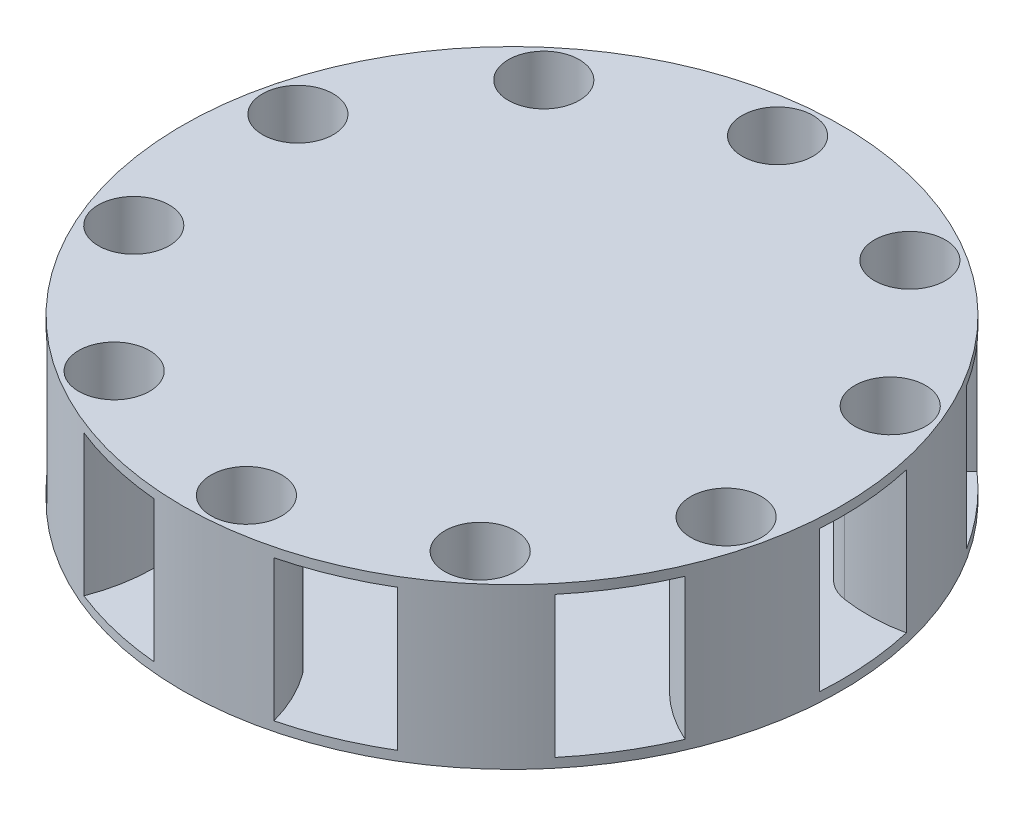
SolidWorks part; units mm, degrees
material "6061 Alloy"
ref_plane "Front Plane" through (0, 0, 0) normal (0, 0, 1) x (1, 0, 0)
ref_plane "Top Plane" through (0, 0, 0) normal (0, 1, 0) x (1, 0, 0)
ref_plane "Right Plane" through (0, 0, 0) normal (1, 0, 0) x (0, 0, -1)
sketch "Sketch1" plane through (0, 0, 0) normal (0, 1, 0) x (1, 0, 0)
  circle A0 centre (0, 0) radius 70
  dimension "D1" = 140
extrude "Boss-Extrude1" add sketch "Sketch1" against normal blind 2
sketch "Sketch2" plane through (0, 0, 0) normal (0, 1, 0) x (1, 0, 0)
  circle A0 centre (-56.7785, -23.5664) radius 8.525
  circle A1 centre (-56.7785, -23.5664) radius 7.525
  circle A2 centre (-59.7868, 14.308) radius 8.525
  circle A3 centre (-59.7868, 14.308) radius 7.525
  circle A4 centre (-39.9585, 46.7172) radius 8.525
  circle A5 centre (-39.9585, 46.7172) radius 7.525
  circle A6 centre (-4.8674, 61.282) radius 8.525
  circle A7 centre (-4.8674, 61.282) radius 7.525
  circle A8 centre (32.0828, 52.4392) radius 8.525
  circle A9 centre (32.0828, 52.4392) radius 7.525
  circle A10 centre (56.7785, 23.5664) radius 8.525
  circle A11 centre (56.7785, 23.5664) radius 7.525
  circle A12 centre (59.7868, -14.308) radius 8.525
  circle A13 centre (59.7868, -14.308) radius 7.525
  circle A14 centre (39.9585, -46.7172) radius 8.525
  circle A15 centre (39.9585, -46.7172) radius 7.525
  circle A16 centre (4.8674, -61.282) radius 8.525
  circle A17 centre (4.8674, -61.282) radius 7.525
  circle A18 centre (-32.0828, -52.4392) radius 8.525
  circle A19 centre (-32.0828, -52.4392) radius 7.525
  point P34 (0, 0)
  dimension "D1" = 17.05
  dimension "D2" = 61.475
  dimension "D3" = 15.05
  dimension "D4" = 10
extrude "Cut-Extrude1" cut sketch "Sketch2" against normal blind 2 contours A3 | A5 | A7 | A9 | A11 | A13 | A15 | A17 | A19 | A1
sketch "Sketch3" plane through (0, 0, 0) normal (0, 1, 0) x (1, 0, 0)
  arc A0 (-42.6484, 38.6277) -> (-31.5498, 48.1207) centre (-39.9585, 46.7172) ccw
  arc A1 (-11.7985, 56.3186) -> (2.7603, 57.4749) centre (-4.8674, 61.282) ccw
  arc A2 (23.558, 52.4977) -> (36.016, 44.8758) centre (32.0828, 52.4392) ccw
  arc A3 (49.9162, 28.6245) -> (55.5149, 15.1356) centre (56.7785, 23.5664) ccw
  arc A4 (57.2081, -6.1823) -> (53.8089, -20.3859) centre (59.7868, -14.308) ccw
  arc A5 (42.6484, -38.6277) -> (31.5498, -48.1207) centre (39.9585, -46.7172) ccw
  arc A6 (11.7985, -56.3186) -> (-2.7603, -57.4749) centre (4.8674, -61.282) ccw
  arc A7 (-23.558, -52.4977) -> (-36.016, -44.8758) centre (-32.0828, -52.4392) ccw
  arc A8 (-49.9162, -28.6245) -> (-55.5149, -15.1356) centre (-56.7785, -23.5664) ccw
  arc A9 (-57.2081, 6.1823) -> (-53.8089, 20.3859) centre (-59.7868, 14.308) ccw
  circle A10 centre (-59.7868, 14.308) radius 6.525
  circle A11 centre (-39.9585, 46.7172) radius 6.525
  circle A12 centre (-4.8674, 61.282) radius 6.525
  circle A13 centre (32.0828, 52.4392) radius 6.525
  circle A14 centre (56.7785, 23.5664) radius 6.525
  circle A15 centre (59.7868, -14.308) radius 6.525
  circle A16 centre (39.9585, -46.7172) radius 6.525
  circle A17 centre (4.8674, -61.282) radius 6.525
  circle A18 centre (-32.0828, -52.4392) radius 6.525
  circle A19 centre (-56.7785, -23.5664) radius 6.525
  arc A20 (23.5578, 52.4392) -> (25.9098, 65.0283) centre (58.9194, 52.3471) cw
  circle A21 centre (0, 0) radius 70 construction
  arc A22 (35.964, 44.8489) -> (46.102, 52.6745) centre (19.7828, 76.2913) ccw
  arc A23 (46.102, 52.6745) -> (25.9098, 65.0283) centre (0, 0) ccw
  arc A24 (49.8817, 28.5772) -> (59.1841, 37.3796) centre (78.4357, 7.7177) cw
  arc A25 (55.4571, 15.1444) -> (68.2586, 15.5165) centre (60.8475, 50.0929) ccw
  arc A26 (68.2586, 15.5165) -> (59.1841, 37.3796) centre (0, 0) ccw
  arc A27 (57.1524, -6.2002) -> (69.8522, -4.5468) centre (67.9922, -39.8596) cw
  arc A28 (53.7674, -20.3447) -> (64.3427, -27.5683) centre (78.6705, 4.7607) ccw
  arc A29 (64.3427, -27.5683) -> (69.8522, -4.5468) centre (0, 0) ccw
  arc A30 (42.5929, -38.6094) -> (53.8391, -44.7365) centre (31.5779, -72.2118) cw
  arc A31 (31.5404, -48.0629) -> (35.8501, -60.1229) centre (66.4441, -42.3899) ccw
  arc A32 (35.8501, -60.1229) -> (53.8391, -44.7365) centre (0, 0) ccw
  arc A33 (11.7643, -56.2711) -> (17.2613, -67.8384) centre (-16.898, -76.9817) cw
  arc A34 (-2.734, -57.4227) -> (-6.336, -69.7127) centre (28.8382, -73.349) ccw
  arc A35 (-6.336, -69.7127) -> (17.2613, -67.8384) centre (0, 0) ccw
  arc A36 (-23.5578, -52.4392) -> (-25.9098, -65.0283) centre (-58.9194, -52.3471) cw
  arc A37 (-35.964, -44.8489) -> (-46.102, -52.6745) centre (-19.7828, -76.2913) ccw
  arc A38 (-46.102, -52.6745) -> (-25.9098, -65.0283) centre (0, 0) ccw
  arc A39 (-49.8817, -28.5772) -> (-59.1841, -37.3796) centre (-78.4357, -7.7177) cw
  arc A40 (-55.4571, -15.1444) -> (-68.2586, -15.5165) centre (-60.8475, -50.0929) ccw
  arc A41 (-68.2586, -15.5165) -> (-59.1841, -37.3796) centre (0, 0) ccw
  arc A42 (-57.1524, 6.2002) -> (-69.8522, 4.5468) centre (-67.9922, 39.8596) cw
  arc A43 (-53.7674, 20.3447) -> (-64.3427, 27.5683) centre (-78.6705, -4.7607) ccw
  arc A44 (-64.3427, 27.5683) -> (-69.8522, 4.5468) centre (0, 0) ccw
  arc A45 (-42.5929, 38.6094) -> (-53.8391, 44.7365) centre (-31.5779, 72.2118) cw
  arc A46 (-31.5404, 48.0629) -> (-35.8501, 60.1229) centre (-66.4441, 42.3899) ccw
  arc A47 (-35.8501, 60.1229) -> (-53.8391, 44.7365) centre (0, 0) ccw
  arc A48 (-11.7643, 56.2711) -> (-17.2613, 67.8384) centre (16.898, 76.9817) cw
  arc A49 (2.734, 57.4227) -> (6.336, 69.7127) centre (-28.8382, 73.349) ccw
  arc A50 (6.336, 69.7127) -> (-17.2613, 67.8384) centre (0, 0) ccw
  point P107 (0, 0)
  circle M2 centre (-56.7785, -23.5664) radius 7.525
  circle M3 centre (-32.0828, -52.4392) radius 7.525
  circle M4 centre (4.8674, -61.282) radius 7.525
  circle M5 centre (39.9585, -46.7172) radius 7.525
  circle M6 centre (59.7868, -14.308) radius 7.525
  circle M7 centre (56.7785, 23.5664) radius 7.525
  circle M8 centre (32.0828, 52.4392) radius 7.525
  circle M9 centre (-4.8674, 61.282) radius 7.525
  circle M10 centre (-39.9585, 46.7172) radius 7.525
  circle M11 centre (-59.7868, 14.308) radius 7.525
  circle M12 centre (0, 0) radius 70
  dimension "D1" = 10
extrude "Boss-Extrude3" add sketch "Sketch3" against normal blind 32 contours A0 A46 A45 M12 M10 | A9 A43 A42 M12 M11 | A8 A40 A39 M12 M2 | A7 A37 A36 M12 M3 | A6 A34 A33 M12 M4 | A5 A31 A30 M12 M5 | A4 A28 A27 M12 M6 | A3 A25 A24 M12 M7 | A2 A22 A20 M12 M8 | A1 A49 A48 M12 M9 region at (-48.3711, 0, -41.4488) region at (-58.9164, 0, -24.211) region at (-5.5193, 0, -69.4889) region at (-61.895, 0, 15.049) region at (36.3707, 0, -59.4477) region at (-41.2245, 0, 48.5612) region at (64.3732, 0, -26.7186) region at (-4.8237, 0, 63.5133) region at (67.7895, 0, 16.2232) region at (33.4497, 0, 54.2115)
sketch "Sketch4" plane through (0, -32, 0) normal (0, -1, 0) x (1, 0, 0)
  circle A0 centre (0, 0) radius 70
extrude "Boss-Extrude4" add sketch "Sketch4" along normal blind 2
sketch "Sketch5" plane through (0, 0, 0) normal (0, 1, 0) x (1, 0, 0)
  circle A0 centre (39.9585, -46.7172) radius 7.525
